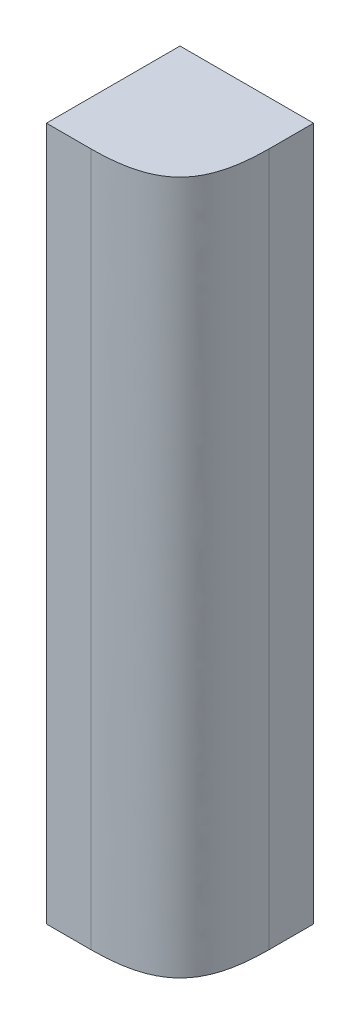
SolidWorks part; units mm, degrees
ref_plane "Front Plane" through (0, 0, 0) normal (0, 0, 1) x (1, 0, 0)
ref_plane "Top Plane" through (0, 0, 0) normal (0, 1, 0) x (1, 0, 0)
ref_plane "Right Plane" through (0, 0, 0) normal (1, 0, 0) x (0, 0, -1)
sketch "Sketch1" plane through (0, 0, 0) normal (0, 1, 0) x (1, 0, 0)
  line L1 (0, 0) -> (36, 0)
  line L2 (0, 0) -> (0, 36)
  line L3 (0, 36) -> (36, 36)
  line L4 (36, 0) -> (36, 36)
  dimension "D1" = 36
  dimension "D2" = 36
extrude "Boss-Extrude1" add sketch "Sketch1" along normal blind 186.9
fillet "Fillet1" radius 24 1 edges at (36, 93.45, 0) conic rho 0.55
sketch "Sketch2" plane through (0, 0, 0) normal (0, -1, 0) x (1, 0, 0)
  line L0 (36, -24) -> (36, -36) construction
  line L1 (0, -12.5) -> (14.28, -12.5)
  line L2 (0, -12.5) -> (0, -36)
  line L3 (0, -36) -> (14.28, -36)
  line L4 (14.28, -12.5) -> (14.28, -36)
  line L5 (0, 0) -> (12, 0) construction
  line L6 (0, -36) -> (0, 0) construction
  line L7 (36, -36) -> (0, -36) construction
  dimension "D1" = 21.72
  dimension "D2" = 12.5
  dimension "D3" = 0
  dimension "D4" = 0
extrude "Cut-Extrude1" cut sketch "Sketch2" against normal blind 27
sketch "Sketch3" plane through (0, 27, 0) normal (0, -1, 0) x (1, 0, 0)
  line L0 (0, -12.5) -> (0, -36) construction
  line L1 (0, -15) -> (11.78, -15)
  line L2 (0, -15) -> (0, -36)
  line L3 (0, -36) -> (11.78, -36)
  line L4 (11.78, -15) -> (11.78, -36)
  line L5 (0, -36) -> (14.28, -36) construction
  line L6 (14.28, -12.5) -> (0, -12.5) construction
  line L7 (14.28, -36) -> (14.28, -12.5) construction
  dimension "D1" = 2.5
  dimension "D2" = 2.5
extrude "Cut-Extrude2" cut sketch "Sketch3" against normal blind 8
